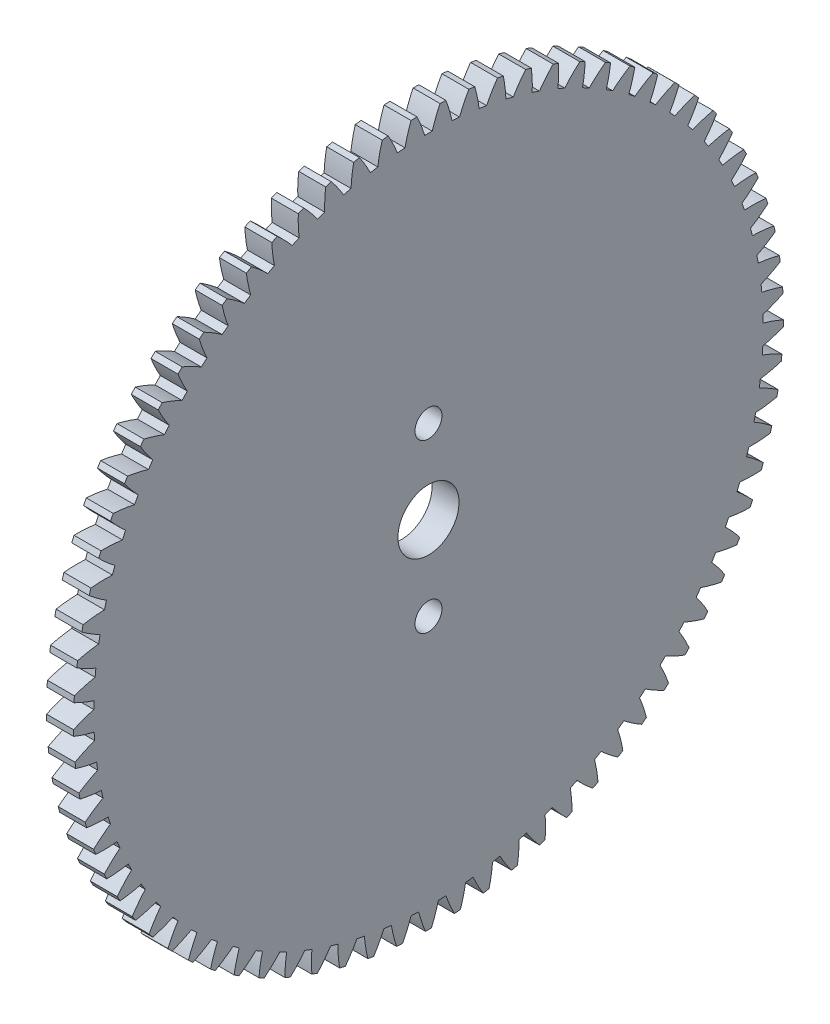
SolidWorks part; units mm, degrees
ref_plane "Plane1" through (0, 0, 0) normal (0, 0, 1) x (1, 0, 0)
ref_plane "Plane2" through (0, 0, 0) normal (0, 1, 0) x (1, 0, 0)
ref_plane "Plane3" through (0, 0, 0) normal (1, 0, 0) x (0, 0, -1)
sketch "HoldingSke" plane through (0, 0, 0) normal (0, 1, 0) x (1, 0, 0)
  line L0 (0, 0) -> (0.225, -0.9744)
  line L1 (-15, 0) -> (100, 0) construction
  line L2 (0, 0) -> (-2.1039, 2.3779)
  line L3 (0, 0) -> (-11.863, 4.5341)
  line L4 (0, 0) -> (1.9427, 8.4147)
  line L5 (0, 0) -> (-46.8476, -17.4728)
  line L6 (0, 0) -> (-1.6579, -1.1186)
  line L7 (-2.1039, 2.3779) -> (8.6586, 51.2059)
  line L8 (-76.2, 54.61) -> (-76.1, 54.61)
  line L9 (-71.009, 38.7566) -> (-53.1078, 45.2721)
  line L10 (-76.2, 71.12) -> (104.1128, 71.12)
  line L11 (0, 0) -> (-2, 0)
  line L12 (-76.2, 101.6) -> (-76.162, 101.6)
  line L13 (24.9733, 27.94) -> (52.9518, 28.4284)
  line L14 (24.9733, 27.94) -> (24.9743, 27.94)
  line L15 (24.9733, 27.94) -> (100.4006, 29.5858)
  line L16 (-63.627, -1) -> (-12.827, -1)
  circle A0 centre (0, 0) radius 0.5
  circle A1 centre (0, 0) radius 37.249
  circle A2 centre (0, 0) radius 37.5
  circle A3 centre (0, 0) radius 0.5
  dimension "MHD" = 74.498
  dimension "Hub_dia" = 75
  dimension "Bore" = 1
  dimension "MBD" = 1
  dimension "Num_teeth" = 77
  dimension "Pitch" = 1
  dimension "Overall_len" = 50
  dimension "Show_teeth" = 77
  dimension "Thickness" = 2
  dimension "OAL" = 50.0001
  dimension "T_dim" = 0.1
  dimension "Ap" = 20
  dimension "H" = 19.05
  dimension "Pitch_radius" = 180.3128
  dimension "Width" = 2
  dimension "Backlash" = 0.038
  dimension "Addendum_fac" = 1
  dimension "Dedendum_fac" = 1.25
  dimension "Clearance_fac" = 0.25
  dimension "Dedendum_add" = 0.001
  dimension "Module" = 1
sketch "BasProSke" plane through (0, 0, 0) normal (0, 1, 0) x (1, 0, 0)
  line L0 (-10, 0) -> (60, 0) construction
  line L1 (0, 0) -> (0, 39.5)
  line L2 (0, 0) -> (2, 0)
  line L3 (2, 0) -> (2, 39.5)
  line L4 (2, 39.5) -> (0, 39.5)
  dimension "Thickness" = 2
  dimension "Diameter" = 79
revolve "Base-Revolve" add sketch "BasProSke" angle 360 about L0
sketch "TooCutSke" plane through (0, 0, 0) normal (1, 0, 0) x (0, 0, -1)
  line L1 (0, 0) -> (0, 107) construction
  line L2 (0, 0) -> (-0.8518, 38.4906) construction
  line L3 (0, 0) -> (-3.1402, 76.9225) construction
  line L4 (-0.8518, 38.4906) -> (-1.5701, 38.4613) construction
  arc A0 (0.4217, 37.2466) -> (-0.4217, 37.2466) centre (0, 0) ccw
  arc A1 (1.2943, 39.5042) -> (-1.2943, 39.5042) centre (0, 0) ccw
  circle A2 centre (0, 0) radius 38.5 construction
  circle A3 centre (0, 0) radius 36.1782 construction
  arc A4 (-0.4217, 37.2466) -> (-1.2943, 39.5042) centre (-15.1779, 32.8404) ccw
  arc A5 (1.2943, 39.5042) -> (0.4217, 37.2466) centre (15.1779, 32.8404) ccw
  dimension "Root_dia" = 74.498
  dimension "Overcut_dia" = 79.0508
  dimension "Pitch_dia" = 77
  dimension "Base_dia" = 72.3563
  dimension "Flank_rad" = 15.4
  dimension "Half_ang" = 2.338
  dimension "Half_CT" = 0.7188
extrude "ToothCut" cut sketch "TooCutSke" along normal through all
fillet "Breaks" [suppressed] radius 0.02 tangent propagation no
fillet "RootFillets" [suppressed] radius 0.251
pattern_circular "TeethCuts" count 77 every 4.675 about axis through (-10, 0, 0) along (1, 0, 0) of "ToothCut", "RootFillets", "Breaks"
sketch "HubNeaOneSke" plane through (0, 0, 0) normal (-1, 0, 0) x (0, 0, 1)
  circle A0 centre (0, 0) radius 37.249
  dimension "Diameter" = 74.498
extrude "HubNearOne" [suppressed] add sketch "HubNeaOneSke" along normal blind 48.0001
sketch "HubNeaBotSke" plane through (0, 0, 0) normal (-1, 0, 0) x (0, 0, 1)
  circle A0 centre (0, 0) radius 37.249
  dimension "Diameter" = 74.498
extrude "HubNearBoth" [suppressed] add sketch "HubNeaBotSke" along normal blind 24
ref_plane "FarPln" through (2, 0, 0) normal (1, 0, 0) x (0, 0, -1)
sketch "HubFarSke" plane through (2, 0, 0) normal (1, 0, 0) x (0, 0, -1)
  circle A0 centre (0, 0) radius 37.249
  dimension "Diameter" = 74.498
extrude "HubFar" [suppressed] add sketch "HubFarSke" along normal blind 24
sketch "BorSke" plane through (0, 0, 0) normal (1, 0, 0) x (0, 0, -1)
  circle A0 centre (0, 0) radius 3.4
  circle A1 centre (0, -9.3) radius 1.5
  circle A2 centre (0, 9.3) radius 1.5
  dimension "Diameter" = 6.8
  dimension "D3" = 3
  dimension "D4" = 3
  dimension "D1" = 9.3
  dimension "D2" = 9.3
extrude "Bore" cut sketch "BorSke" along normal mid plane 100.0001
sketch "KeySke" plane through (0, 0, 0) normal (1, 0, 0) x (0, 0, -1)
  line L0 (-0.05, 0) -> (-0.05, 0.6)
  line L1 (-0.05, 0.6) -> (0.05, 0.6)
  line L2 (0.05, 0.6) -> (0.05, 0)
  line L3 (0, 0) -> (0, 34) construction
  line L4 (-0.05, 0) -> (0.05, 0)
  dimension "Offset" = 0.6
  dimension "Width" = 0.1
extrude "Keyway" [suppressed] cut sketch "KeySke" along normal mid plane 100.0001
pattern_circular "Keyway2" [suppressed] count 2 every 90 about axis through (-10, 0, 0) along (1, 0, 0) reverse direction yes
scale "Scale1" scale about centroid uniform scaling no x scale factor 1.5 y scale factor 1 z scale factor 1
equation "' \"Module@HoldingSke\" = 6.35"
equation "' \"Num_teeth@HoldingSke\" = 12"
equation "' \"Ap@HoldingSke\" =  20"
equation "' \"Ap@HoldingSke\" = 20"
equation "' \"Width@HoldingSke\" = 0.5 * 25.4"
equation "' \"Hub_dia@HoldingSke\"= 1 * 25.4"
equation "' \"Hub_dia@HoldingSke\" = 1 * 25.4"
equation "' \"Overall_len@HoldingSke\" = 1.0 * 25.4"
equation "' \"Bore@HoldingSke\" = 0.75 * 25.4"
equation "' \"T_dim@HoldingSke\" = 0.1 * 25.4"
equation "' \"Width@KeySke\" = 0.25 * 25.4"
equation "' \"Show_teeth@HoldingSke\" = 13"
equation "' \"Backlash@HoldingSke\" = 0.009 * 25.4"
equation "' \"Addendum_fac@HoldingSke\" = 1.0"
equation "' \"Dedendum_fac@HoldingSke\" = 1.25"
equation "' \"Dedendum_add@HoldingSke\" = 0.00005 * 25.4"
equation "' \"Clearance_fac@HoldingSke\" = 0.25"
equation "\"Pitch@HoldingSke\" = 1 / \"Module@HoldingSke\""
equation "\"Overcut_dia@TooCutSke\" = (\"Num_teeth@HoldingSke\" + 2 * \"Addendum_fac@HoldingSke\") / \"Pitch@HoldingSke\" + 0.002 * 25.4"
equation "\"Pitch_dia@TooCutSke\" = \"Num_teeth@HoldingSke\" / \"Pitch@HoldingSke\""
equation "\"Base_dia@TooCutSke\" = \"Num_teeth@HoldingSke\" / \"Pitch@HoldingSke\" * cos((\"Ap@HoldingSke\"  * 3.14159265 / 180))"
equation "\"Root_dia@TooCutSke\" = (\"Num_teeth@HoldingSke\" + 2) / \"Pitch@HoldingSke\" - 2 * (\"Addendum_fac@HoldingSke\" + \"Dedendum_fac@HoldingSke\") / \"Pitch@HoldingSke\" - \"Dedendum_add@HoldingSke\" * 2"
equation "\"Half_ang@TooCutSke\" = 180 / \"Num_teeth@HoldingSke\""
equation "\"Half_CT@TooCutSke\" = \"Num_teeth@HoldingSke\" / \"Pitch@HoldingSke\" * sin((3.14159265 / 2 / \"Num_teeth@HoldingSke\")) / 2 - 7 * \"Backlash@HoldingSke\" / 4"
equation "\"Flank_rad@TooCutSke\" = \"Num_teeth@HoldingSke\" / \"Pitch@HoldingSke\" / 5"
equation "\"Radius@RootFillets\" = \"Clearance_fac@HoldingSke\" / \"Pitch@HoldingSke\" + \"Dedendum_add@HoldingSke\""
equation "\"Break_rad@Breaks\" = 0.02 / \"Pitch@HoldingSke\""
equation "\"Thickness@HoldingSke\" = \"Width@HoldingSke\""
equation "\"OAL@HoldingSke\" = \"Thickness@HoldingSke\""
equation "\"MHD@HoldingSke\" = (\"Num_teeth@HoldingSke\" + 2) / \"Pitch@HoldingSke\" - 2 * (\"Addendum_fac@HoldingSke\" + \"Dedendum_fac@HoldingSke\")  / \"Pitch@HoldingSke\" - \"Dedendum_add@HoldingSke\" * 2"
equation "\"MBD@HoldingSke\" = (\"Num_teeth@HoldingSke\" + 2) / \"Pitch@HoldingSke\" - 2 * (\"Addendum_fac@HoldingSke\" + \"Dedendum_fac@HoldingSke\")  / \"Pitch@HoldingSke\" - \"Dedendum_add@HoldingSke\" * 2 - 0.002 * 25.4"
equation "\"MHD@HoldingSke\" = ((sgn( \"MHD@HoldingSke\" - \"Hub_dia@HoldingSke\" )-1)*( \"MHD@HoldingSke\" - \"Hub_dia@HoldingSke\" ))/-2+ \"Hub_dia@HoldingSke\""
equation "\"MBD@HoldingSke\" = ((sgn( \"MBD@HoldingSke\" - \"Bore@HoldingSke\" )-1)*( \"MBD@HoldingSke\" - \"Bore@HoldingSke\" ))/-2+ \"Bore@HoldingSke\""
equation "\"OAL@HoldingSke\" = ((sgn( \"OAL@HoldingSke\" - \"Overall_len@HoldingSke\" )+1)*( \"OAL@HoldingSke\" - \"Overall_len@HoldingSke\" ))/2 + \"Overall_len@HoldingSke\" + 0.000002 * 25.4"
equation "\"Num_teeth@TeethCuts\" = int( \"Show_teeth@HoldingSke\" ) + 1"
equation "\"Num_teeth@TeethCuts\" = ((sgn( \"Num_teeth@TeethCuts\" - \"Num_teeth@HoldingSke\" )-1)*( \"Num_teeth@TeethCuts\" - \"Num_teeth@HoldingSke\" ))/-2+ \"Num_teeth@HoldingSke\""
equation "\"Num_teeth@TeethCuts\" = ((sgn( \"Num_teeth@TeethCuts\" - 2.0)+1)*( \"Num_teeth@TeethCuts\" - 2.0))/2 +2.0"
equation "\"Angle@TeethCuts\" = 360.0 / \"Num_teeth@HoldingSke\""
equation "\"Diameter@BasProSke\" = (\"Num_teeth@HoldingSke\" + 2 * \"Addendum_fac@HoldingSke\") / \"Pitch@HoldingSke\""
equation "\"Thickness@BasProSke\"  = \"Thickness@HoldingSke\""
equation "' \"Fillet_rad@BasProSke\" =  \"Thickness@HoldingSke\" * 0.05"
equation "' \"Fillet_rad@BasProSke\" = \"Thickness@HoldingSke\" * 0.05"
equation "\"MHD@HoldingSke\" = ((sgn( \"MHD@HoldingSke\" - \"Root_dia@TooCutSke\" )-1)*( \"MHD@HoldingSke\" - \"Root_dia@TooCutSke\" ))/-2+ \"Root_dia@TooCutSke\""
equation "\"Diameter@HubNeaOneSke\" = \"MHD@HoldingSke\""
equation "\"Length@HubNearOne\" = \"OAL@HoldingSke\" - \"Thickness@BasProSke\""
equation "\"Diameter@HubNeaBotSke\" = \"MHD@HoldingSke\""
equation "\"Length@HubNearBoth\" = ( \"OAL@HoldingSke\" - \"Thickness@BasProSke\" ) / 2.0"
equation "\"Thickness@FarPln\" = \"Thickness@BasProSke\""
equation "\"Diameter@HubFarSke\" = \"MHD@HoldingSke\""
equation "\"Length@HubFar\" = ( \"OAL@HoldingSke\" - \"Thickness@BasProSke\" ) / 2.0"
equation "\"Diameter@BorSke\"=6.8mm"
equation "\"D1@Bore\" = \"OAL@HoldingSke\" * 2.0"
equation "\"D1@Keyway\" = \"OAL@HoldingSke\" * 2.0"
equation "\"Offset@KeySke\" = \"T_dim@HoldingSke\" + \"MBD@HoldingSke\" / 2.0"
